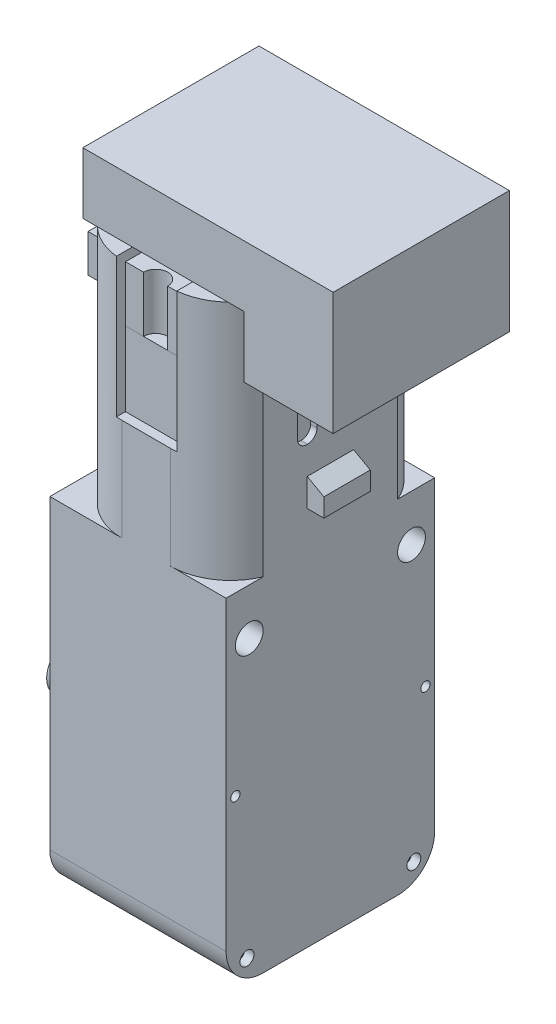
SolidWorks part; units mm, degrees
ref_plane "Alzado" through (0, 0, 0) normal (1, 0, 0) x (0, 1, 0)
ref_plane "Planta" through (0, 0, 0) normal (0, 0, 1) x (0, 1, 0)
ref_plane "Vista lateral" through (0, 0, 0) normal (0, 1, 0) x (-1, 0, 0)
sketch "Croquis1" plane through (0, 0, 0) normal (1, 0, 0) x (0, 1, 0)
  line L1 (-4.84, 11.25) -> (29.66, 11.25)
  line L2 (-7.34, 8.75) -> (-7.34, -8.75)
  line L3 (-4.84, -11.25) -> (29.66, -11.25)
  line L4 (29.66, 11.25) -> (29.66, -11.25)
  line L6 (5.66, 10.25) -> (-4.84, -8.75)
  line L8 (-4.84, 8.75) -> (5.66, -10.25)
  line L9 (-4.84, 0) -> (-0.0045, 0)
  arc A0 (-4.84, -11.25) -> (-7.34, -8.75) centre (-4.84, -8.75) cw
  arc A1 (-4.84, 11.25) -> (-7.34, 8.75) centre (-4.84, 8.75) ccw
  circle A2 centre (5.66, -10.25) radius 0.5
  circle A3 centre (5.66, 10.25) radius 0.5
  circle A4 centre (-0.0045, 0) radius 2.7322
  point P6 (-7.34, -11.25)
  point P9 (-7.34, 11.25)
  point P10 (-7.34, 0)
  dimension "D2" = 2.5
  dimension "D5" = 1
  dimension "D1" = 22.5
  dimension "D3" = 37
  dimension "D8" = 2.5
extrude "Saliente-Extruir2" add sketch "Croquis1" along normal blind 9.5 and the other way blind 9.5 contours L1 A1 L2 A0 L3 L4 A4 A2 A3 | A3 | L9 A4 L6 | L6 A4 L8 | L8 A4 L6 | L6 A4 L8 | L8 A4 L9 | A2 region at (0, 11.5559, 0) region at (0, 5.9069, -9.8315) region at (0, 1.4911, 0) region at (0, -0.0045, 1.745) region at (0, 5.4131, 10.6685) region at (0, -0.0045, -1.745) region at (0, -1.5001, 0.8823) region at (0, -1.5001, -0.8823)
sketch "Croquis2" plane through (0, 0, 0) normal (1, 0, 0) x (0, 1, 0)
  line L0 (-11.84, 3.2804) -> (-10.84, 3.2804)
  line L1 (-7.34, 8.75) -> (-7.34, -8.75) construction
  line L2 (-11.84, -2.5) -> (-11.84, 2.5)
  line L3 (-11.84, 0) -> (-13.0585, 0)
  line L4 (-11.84, -2.5) -> (-7.34, -2.5)
  line L5 (-11.84, -2.5) -> (-11.84, 2.5)
  line L6 (-11.84, 2.5) -> (-7.34, 2.5)
  line L7 (-7.34, -2.5) -> (-7.34, 2.5)
  line L8 (-11.84, -1.34) -> (-11.84, 1.34)
  line L10 (-12.4811, -2.5) -> (-12.4811, -1.5)
  line L11 (-12.4811, 2.5) -> (-12.4811, 1.5)
  circle A0 centre (-9.34, 0) radius 1.5
  dimension "D3" = 1
  dimension "D4" = 4.5
  dimension "D1" = 1
  dimension "D2" = 1
  dimension "D5" = 5
extrude "Saliente-Extruir4" add sketch "Croquis2" along normal blind 1.3 and the other way blind 1.3 contours L4 L7 L6 L5 L2 A0 region at (0, -11.7727, -1.92)
sketch "Croquis3" plane through (-9.5, 0, 0) normal (-1, 0, 0) x (0, -1, 0)
  circle A0 centre (0, 0) radius 2.5
extrude "Cortar-Extruir1" cut sketch "Croquis3" against normal blind 5
sketch "Croquis4" plane through (-9.5, 0, 0) normal (-1, 0, 0) x (0, 0, 1)
  line L0 (-12.6785, 24.66) -> (-12.6785, 5.66)
  line L2 (-11.25, 25.9631) -> (-10.25, 25.9631)
  line L3 (0, -7.34) -> (0, -15.1717)
  line L4 (8.75, -7.34) -> (-8.75, -7.34) construction
  line L5 (11.25, 25.9631) -> (10.25, 25.9631)
  line L6 (10.25, 25.9631) -> (10.25, 5.66)
  line L8 (-10.25, 4.4941) -> (-10.25, 25.9631)
  circle A0 centre (9.75, 5.66) radius 0.5
  circle A1 centre (8.75, -4.84) radius 0.75
  circle A2 centre (-9.75, 5.66) radius 0.5
  circle A3 centre (-8.75, -4.84) radius 0.75
  circle A4 centre (8.75, -4.84) radius 0.75
  circle A5 centre (9.75, 5.66) radius 0.5
  circle A6 centre (-9.75, 5.66) radius 0.5
  circle A7 centre (-8.75, -4.84) radius 0.75
  circle A8 centre (-8.75, -4.84) radius 0.75
  dimension "D3" = 1
  dimension "D4" = 1.5
  dimension "D1" = 19
  dimension "D2" = 1
sketch "Croquis5" plane through (9.5, 0, 0) normal (1, 0, 0) x (0, 1, 0)
  circle A0 centre (-4.84, 8.75) radius 0.75
  circle A1 centre (5.66, 9.75) radius 0.5
  circle A2 centre (5.66, -9.75) radius 0.5
  circle A3 centre (-4.84, -8.75) radius 0.75
extrude "Cortar-Extruir2" cut sketch "Croquis5" against normal blind 1
extrude "Cortar-Extruir3" cut sketch "Croquis4" against normal blind 1 contours A0 | A1 | A3 | A2 region at (-9.5, 5.66, 9.75) region at (-9.5, -4.84, 8.75) region at (-9.5, -4.84, -8.75)
sketch "Croquis6" plane through (-9.5, 0, 0) normal (-1, 0, 0) x (0, 0, 1)
  line L0 (13.1737, 24.66) -> (13.1737, 10.66)
  circle A0 centre (0, 10.66) radius 2
  dimension "D2" = 4
  dimension "D1" = 14
extrude "Saliente-Extruir6" add sketch "Croquis6" along normal blind 2 contours A0 region at (-9.5, 10.66, 0)
sketch "Croquis7" plane through (-9.5, 0, 0) normal (-1, 0, 0) x (0, 0, 1)
  line L0 (-11.25, 26.5829) -> (-10.25, 26.5829)
  line L1 (-12.8476, 24.66) -> (-12.8476, 19.66)
  line L2 (-10.25, 26.5829) -> (-10.25, 19.66)
  line L3 (-10.25, 19.66) -> (-12.8476, 19.66)
  line L4 (0, -11.84) -> (0, -18.0156)
  line L5 (-2.5, -11.84) -> (2.5, -11.84) construction
  line L7 (-7.25, 19.66) -> (-7.25, 21.16)
  line L8 (-7.25, 21.16) -> (-11.25, 21.16)
  circle A0 centre (-8.75, 19.66) radius 1.5
  circle A1 centre (8.75, 19.66) radius 1.5
  dimension "D1" = 1
  dimension "D2" = 5
  dimension "D3" = 1.5
  dimension "D4" = 4
extrude "Cortar-Extruir4" cut sketch "Croquis7" against normal through all contours A0 | A1 region at (-9.5, 19.66, -8.75)
sketch "Croquis8" plane through (0, 29.66, 0) normal (0, 1, 0) x (-1, 0, 0)
  line L1 (-3.5, 11.25) -> (1.7, 11.25)
  line L2 (-9.5, 7.25) -> (-9.5, -7.25)
  line L3 (-3.5, -11.25) -> (1.7, -11.25)
  line L4 (7.7, 7.25) -> (7.7, -7.25)
  line L5 (11.5, 0) -> (15.9145, 0)
  line L7 (11.5, -2) -> (11.5, 2) construction
  line L8 (0, 0) -> (0, 0.7272)
  arc A2 (7.7, 7.25) -> (1.7, 11.25) centre (1.7, 4.75) ccw
  arc A3 (7.7, -7.25) -> (1.7, -11.25) centre (1.7, -4.75) cw
  arc A5 (-3.5, 11.25) -> (-9.5, 7.25) centre (-3.5, 4.75) ccw
  arc A11 (-3.5, -11.25) -> (-9.5, -7.25) centre (-3.5, -4.75) cw
extrude "Saliente-Extruir7" add sketch "Croquis8" along normal blind 26 contours A11 A3 L4 A2 A5 region at (0.9, 29.66, 0)
sketch "Croquis9" plane through (-9.5, 0, 0) normal (-1, 0, 0) x (0, -1, 0)
  line L3 (-8.66, 15.3575) -> (-8.66, -16.1606) construction
  line L4 (-8.66, 15.3575) -> (18.8238, 15.3575)
  line L5 (-8.66, 15.3575) -> (-8.66, -16.1606)
  line L6 (-8.66, -16.1606) -> (18.8238, -16.1606)
  line L7 (18.8238, 15.3575) -> (18.8238, -16.1606)
extrude "Cortar-Extruir5" cut sketch "Croquis9" against normal through all
sketch "Croquis10" plane through (0, 8.66, 0) normal (0, -1, 0) x (-1, 0, 0)
  line L1 (9.5, -11.25) -> (-9.5, -11.25)
  line L2 (9.5, -11.25) -> (9.5, 11.25)
  line L3 (9.5, 11.25) -> (-9.5, 11.25)
  line L4 (-9.5, -11.25) -> (-9.5, 11.25)
sketch "Croquis11" plane through (-9.5, 0, 0) normal (-1, 0, 0) x (0, 0, 1)
  line L1 (13.3634, 18.0947) -> (-15.0337, 18.0947)
  line L2 (13.3634, 18.0947) -> (13.3634, 2.7979)
  line L3 (13.3634, 2.7979) -> (-15.0337, 2.7979)
  line L4 (-15.0337, 18.0947) -> (-15.0337, 2.7979)
extrude "Cortar-Extruir7" cut sketch "Croquis11" against normal through all and the other way through all
sketch "Croquis12" plane through (-9.5, 0, 0) normal (-1, 0, 0) x (0, 0, 1)
  line L0 (-11.25, 29.66) -> (-11.25, 22.66)
  line L1 (-11.25, 18.0947) -> (-11.25, 29.66) construction
  line L3 (-11.25, 22.66) -> (12.1047, 22.66)
  line L4 (-11.25, 22.66) -> (-11.25, 15.491)
  line L5 (-11.25, 15.491) -> (12.1047, 15.491)
  line L6 (12.1047, 22.66) -> (12.1047, 15.491)
  line M2 (-11.25, 29.66) -> (-11.25, 18.0947)
  line M3 (-11.25, 18.0947) -> (11.25, 18.0947)
  line M4 (11.25, 18.0947) -> (11.25, 29.66)
  circle M6 centre (8.75, 19.66) radius 1.5
  circle M7 centre (-8.75, 19.66) radius 1.5
  dimension "D1" = 7
extrude "Cortar-Extruir8" cut sketch "Croquis12" against normal through all contours L3 M2 M3 M4 M6 M7 | L6 L3 L4 L5 M4 M3 region at (-9.5, 20.4918, 0) region at (-9.5, 17.009, 1.1057)
sketch "Croquis14" plane through (0, 22.66, 0) normal (0, -1, 0) x (-1, 0, 0)
  line L1 (9.5, -11.25) -> (-9.5, -11.25)
  line L2 (9.5, -11.25) -> (9.5, 11.25)
  line L3 (9.5, 11.25) -> (-9.5, 11.25)
  line L4 (-9.5, -11.25) -> (-9.5, 11.25)
extrude "Saliente-Extruir9" add sketch "Croquis14" along normal blind 30
sketch "Croquis15" plane through (-9.5, 0, 0) normal (-1, 0, 0) x (0, 0, 1)
  line L0 (0, -7.34) -> (0, -12.8155)
  line L1 (11.25, -7.34) -> (-11.25, -7.34) construction
  line L2 (-11.25, 29.66) -> (-10.25, 29.66)
  line L3 (-7.25, 29.66) -> (-11.25, 29.66) construction
  line L4 (-11.25, 29.66) -> (-11.25, 24.66)
  line L5 (-11.25, -7.34) -> (-11.25, 29.66) construction
  line L6 (-11.25, 24.66) -> (-10.25, 24.66)
  line L7 (-10.25, 24.66) -> (-10.25, 29.66)
  circle A0 centre (-8.75, 24.66) radius 1.5
  circle A1 centre (8.75, 24.66) radius 1.5
  dimension "D3" = 3
  dimension "D1" = 5
  dimension "D2" = 1
extrude "Cortar-Extruir9" cut sketch "Croquis15" against normal through all contours A1 | A0 region at (-9.5, 24.66, -8.75) region at (-9.5, 24.66, 8.75)
sketch "Croquis16" plane through (-9.5, 0, 0) normal (-1, 0, 0) x (0, 0, 1)
  line L0 (11.25, 29.66) -> (11.25, 15.66)
  line L1 (11.25, -7.34) -> (11.25, 29.66) construction
  circle A0 centre (0, 15.66) radius 2
  dimension "D2" = 4
  dimension "D1" = 14
extrude "Saliente-Extruir10" add sketch "Croquis16" along normal blind 2 contours A0 region at (-9.5, 15.66, 0)
sketch "Croquis17" plane through (-9.5, 0, 0) normal (-1, 0, 0) x (0, 0, 1)
  line L0 (11.25, 29.66) -> (11.25, 10.66)
  line L1 (11.25, -7.34) -> (11.25, 29.66) construction
  line L2 (11.25, 10.66) -> (10.75, 10.66)
  line L3 (11.25, -7.34) -> (-11.25, -7.34) construction
  line L4 (14.7504, -3.34) -> (14.7504, -7.34)
  line L5 (9.75, 10.66) -> (9.75, -12.757)
  line L6 (11.25, -3.34) -> (-13.714, -3.34)
  line L7 (11.25, -7.34) -> (7.25, -3.34)
  line L8 (0, -7.34) -> (0, -17.085)
  line L9 (-11.25, -3.34) -> (-11.25, -7.34)
  line L10 (-11.25, -7.34) -> (-7.25, -7.34)
  line L11 (-7.25, -7.34) -> (7.25, -7.34)
  line L12 (7.25, -7.34) -> (11.25, -7.34)
  line L13 (11.25, -3.34) -> (11.25, -7.34)
  line L14 (11.25, -7.34) -> (7.25, -7.34)
  line L15 (11.25, -3.34) -> (11.25, -7.34)
  circle A0 centre (10.25, 10.66) radius 0.5
  arc A1 (7.25, -7.34) -> (9.75, -0.2175) centre (7.25, -3.34) ccw
  circle A4 centre (9, -5.09) radius 0.75
  circle A5 centre (-9, -5.09) radius 0.75
  arc A6 (-7.25, -7.34) -> (-11.25, -3.34) centre (-7.25, -3.34) cw
  circle A7 centre (-10.25, 10.66) radius 0.5
  arc A8 (7.25, -7.34) -> (11.25, -3.34) centre (7.25, -3.34) ccw
  dimension "D3" = 1
  dimension "D4" = 8
  dimension "D5" = 1.5
  dimension "D1" = 19
  dimension "D2" = 0.5
sketch "Croquis18" plane through (-9.5, 0, 0) normal (-1, 0, 0) x (0, 0, 1)
extrude "Cortar-Extruir10" cut sketch "Croquis17" against normal through all contours A0 | A4 L7 | L7 A4 | A7 | A5 region at (-9.5, 10.66, 10.25) region at (-9.5, -4.8649, 9.2251) region at (-9.5, -5.3151, 8.7749) region at (-9.5, 10.66, -10.25)
sketch "Croquis19" plane through (-9.5, 0, 0) normal (-1, 0, 0) x (0, 0, 1)
  line L0 (11.25, -7.34) -> (11.25, -3.34)
  line L1 (11.25, -7.34) -> (11.25, 29.66) construction
  line L2 (0, -7.34) -> (0, -13.8514)
  line L3 (11.25, -7.34) -> (7.25, -7.34)
  line L4 (11.25, -7.34) -> (-11.25, -7.34) construction
  line L5 (-11.25, -7.34) -> (-7.25, -7.34)
  line L6 (-11.25, -7.34) -> (-11.25, -3.34)
  arc A0 (7.25, -7.34) -> (11.25, -3.34) centre (7.25, -3.34) ccw
  arc A1 (-7.25, -7.34) -> (-11.25, -3.34) centre (-7.25, -3.34) cw
  line M9 (-11.25, 29.66) -> (-11.25, -7.34)
  line M10 (-11.25, -7.34) -> (11.25, -7.34)
  line M11 (11.25, -7.34) -> (11.25, 29.66)
  dimension "D1" = 8
sketch "Croquis20" plane through (0, -7.34, 0) normal (0, -1, 0) x (1, 0, 0)
  line L5 (-8.6868, 10.6536) -> (8.5298, 10.6536)
  line L6 (-8.6868, 10.6536) -> (-8.6868, -10.8334)
  line L7 (-8.6868, -10.8334) -> (8.5298, -10.8334)
  line L8 (8.5298, 10.6536) -> (8.5298, -10.8334)
  line L9 (2.0429, 4.3316) -> (2.816, 4.3316)
  line L10 (2.0429, 4.3316) -> (2.0429, 4.8022)
  line L11 (2.0429, 4.8022) -> (2.816, 4.8022)
  line L12 (2.816, 4.3316) -> (2.816, 4.8022)
extrude "Saliente-Extruir12" add sketch "Croquis20" against normal blind 24 contours L10 L9 L12 L11
sketch "Croquis21" plane through (0, -7.34, 0) normal (0, -1, 0) x (-1, 0, 0)
  line L0 (9.5, -11.25) -> (-9.5, -11.25) construction
  line L1 (8.3272, -11.25) -> (-8.5298, -11.25)
  line L2 (8.3272, -11.25) -> (8.3272, 11.25)
  line L3 (8.3272, 11.25) -> (-8.5298, 11.25)
  line L4 (-8.5298, -11.25) -> (-8.5298, 11.25)
  line L5 (9.5, 11.25) -> (-9.5, 11.25) construction
extrude "Saliente-Extruir13" add sketch "Croquis21" against normal blind 24
extrude "Cortar-Extruir11" cut sketch "Croquis19" against normal through all contours A0 M10 M11 | A1 M10 M9 region at (-9.5, -6.4465, 10.3565) region at (-9.5, -6.4465, -10.3565)
sketch "Croquis22" plane through (-9.5, 0, 0) normal (-1, 0, 0) x (0, 0, 1)
  line L0 (7.25, -7.34) -> (17.3359, -7.34)
  line L1 (11.25, -7.34) -> (11.25, 3.86)
  line L2 (11.25, -3.34) -> (11.25, 29.66) construction
  line L3 (11.25, 3.86) -> (-11.25, 3.86)
  line L4 (-11.25, -3.34) -> (-11.25, 29.66) construction
  circle A0 centre (0, 3.86) radius 2.6
  dimension "D2" = 5.2
  dimension "D1" = 11.2
extrude "Cortar-Extruir12" cut sketch "Croquis22" against normal blind 5 contours L3 A0 | L3 A0 region at (-9.5, 2.7565, 0) region at (-9.5, 4.9635, 0)
sketch "Croquis23" plane through (-9.5, 0, 0) normal (-1, 0, 0) x (0, 0, 1)
  circle A0 centre (0, 3.86) radius 2.6
  circle A1 centre (0, 3.86) radius 2.75
  dimension "D1" = 5.5
extrude "Saliente-Extruir14" add sketch "Croquis23" along normal blind 0.5 draft 8 contours A1 | A0
sketch "Croquis24" plane through (0, -7.34, 0) normal (0, -1, 0) x (1, 0, 0)
  line L1 (-1.25, -2.5) -> (1.25, -2.5)
  line L2 (-1.25, -2.5) -> (-1.25, 2.5)
  line L3 (-1.25, 2.5) -> (1.25, 2.5)
  line L4 (1.25, -2.5) -> (1.25, 2.5)
  line L5 (-1.25, -2.5) -> (1.25, 2.5) construction
  line L6 (-1.25, 2.5) -> (1.25, -2.5) construction
  point P0 (0, 0)
  dimension "D1" = 2.5
  dimension "D2" = 5
extrude "Saliente-Extruir15" add sketch "Croquis24" along normal blind 4.7
sketch "Croquis25" plane through (-1.25, 0, 0) normal (-1, 0, 0) x (0, 0, 1)
  line L0 (2.5, -12.04) -> (-2.5, -12.04) construction
  circle A0 centre (0, -9.64) radius 1.4
  dimension "D1" = 2.8
  dimension "D2" = 2.4
extrude "Cortar-Extruir13" cut sketch "Croquis25" against normal blind 4.7
sketch "Croquis26" plane through (-7.7, 0, 0) normal (-1, 0, 0) x (0, -1, 0)
  line L0 (-29.66, -7.25) -> (-33.66, -7.25)
  line L1 (-55.66, -7.25) -> (-29.66, -7.25) construction
  line L2 (-33.66, -7.25) -> (-33.66, 7.25)
  line L3 (-55.66, 7.25) -> (-29.66, 7.25) construction
  line L5 (-36.66, 2.5) -> (-33.66, 2.5)
  line L6 (-36.66, 2.5) -> (-36.66, -2.5)
  line L7 (-36.66, -2.5) -> (-33.66, -2.5)
  line L8 (-33.66, 2.5) -> (-33.66, -2.5)
  line L9 (-36.66, 2.5) -> (-33.66, -2.5) construction
  line L10 (-36.66, -2.5) -> (-33.66, 2.5) construction
  point P5 (-35.16, 0)
  point P14 (-33.66, 0)
  dimension "D1" = 4
  dimension "D2" = 3
  dimension "D3" = 5
extrude "Saliente-Extruir17" add sketch "Croquis26" along normal blind 2 and the other way blind 19 contours L6 L7 L2 L5 region at (-7.7, 35.16, 0)
sketch "Croquis27" plane through (0, 0, 0) normal (0, 0, 1) x (0, 1, 0)
  line L0 (33.66, 9.7) -> (35.66, 9.7)
  line L1 (36.66, 9.7) -> (33.66, 9.7) construction
  line L2 (35.66, 9.7) -> (35.66, -11.3)
  line L3 (36.66, -11.3) -> (33.66, -11.3) construction
  line L4 (35.66, 9.7) -> (36.66, 7.7)
  line L5 (36.66, 7.7) -> (36.66, 9.7)
  line L6 (36.66, 9.7) -> (35.66, 9.7)
  line L7 (35.66, -11.3) -> (36.66, -9.5)
  line L8 (36.66, -9.5) -> (36.66, -11.3)
  line L9 (36.66, -11.3) -> (35.66, -11.3)
  dimension "D1" = 2
extrude "Cortar-Extruir14" cut sketch "Croquis27" against normal through all and the other way through all contours L5 L6 L4 | L9 L8 L7 region at (10.7, 36.3267, 0) region at (-9.0333, 36.3267, 0)
sketch "Croquis28" plane through (-7.7, 0, 0) normal (-1, 0, 0) x (0, -1, 0)
  line L0 (-36.66, -2.5) -> (-39.66, -2.5)
  line L1 (-36.66, 0) -> (-38.0942, 0)
  line L2 (-45.66, -1.4465) -> (-40.66, -1.4465)
  line L3 (-46.66, -2.4465) -> (-46.66, -2.5535)
  line L4 (-45.66, -3.5535) -> (-40.66, -3.5535)
  line L5 (-39.66, -2.4465) -> (-39.66, -2.5535)
  line L6 (-46.66, -1.4465) -> (-39.66, -3.5535) construction
  line L7 (-46.66, -3.5535) -> (-39.66, -1.4465) construction
  line L8 (-36.66, 2.5) -> (-36.66, -2.5) construction
  line L9 (-45.66, 3.5535) -> (-40.66, 3.5535)
  line L10 (-39.66, 2.4465) -> (-39.66, 2.5535)
  line L11 (-45.66, 1.4465) -> (-40.66, 1.4465)
  line L12 (-46.66, 2.4465) -> (-46.66, 2.5535)
  arc A0 (-45.66, -3.5535) -> (-46.66, -2.5535) centre (-45.66, -2.5535) cw
  arc A1 (-46.66, -2.4465) -> (-45.66, -1.4465) centre (-45.66, -2.4465) cw
  arc A2 (-39.66, -2.5535) -> (-40.66, -3.5535) centre (-40.66, -2.5535) cw
  arc A3 (-39.66, -2.4465) -> (-40.66, -1.4465) centre (-40.66, -2.4465) ccw
  arc A4 (-39.66, 2.5535) -> (-40.66, 3.5535) centre (-40.66, 2.5535) ccw
  arc A5 (-39.66, 2.4465) -> (-40.66, 1.4465) centre (-40.66, 2.4465) cw
  arc A6 (-45.66, 3.5535) -> (-46.66, 2.5535) centre (-45.66, 2.5535) ccw
  arc A7 (-46.66, 2.4465) -> (-45.66, 1.4465) centre (-45.66, 2.4465) ccw
  point P2 (-43.16, -2.5)
  dimension "D3" = 1
  dimension "D1" = 3
  dimension "D2" = 7
extrude "Cortar-Extruir15" cut sketch "Croquis28" against normal through all contours L12 A7 L11 A5 L10 A4 L9 A6 | L2 A3 L5 A2 L4 A0 L3 A1 region at (-7.7, 43.16, 2.5)
sketch "Croquis29" plane through (9.5, 0, 0) normal (1, 0, 0) x (0, 1, 0)
  line L0 (40.66, -1.4465) -> (45.66, -1.4465) construction
  line L5 (36.66, 0) -> (38.1303, 0)
  line L6 (36.66, -2.5) -> (36.66, 2.5) construction
  line L7 (40.66, -3.5535) -> (45.66, -3.5535) construction
  line L8 (40.66, -1.4465) -> (50.66, -1.4465)
  line L13 (40.66, -1.4465) -> (40.66, -3.5535)
  line L14 (40.66, -3.5535) -> (50.66, -3.5535)
  line L15 (51.66, -2.4465) -> (51.66, -2.5535)
  line L16 (40.66, 3.5535) -> (50.66, 3.5535)
  line L17 (51.66, 2.4465) -> (51.66, 2.5535)
  line L18 (40.66, 1.4465) -> (50.66, 1.4465)
  line L19 (40.66, 1.4465) -> (40.66, 3.5535)
  arc A1 (51.8241, -1.5254) -> (51.8281, -1.6145) centre (52.8241, -1.5254) ccw
  arc A2 (51.66, -2.5535) -> (50.66, -3.5535) centre (50.66, -2.5535) cw
  arc A3 (51.66, -2.4465) -> (50.66, -1.4465) centre (50.66, -2.4465) ccw
  arc A4 (51.66, 2.5535) -> (50.66, 3.5535) centre (50.66, 2.5535) ccw
  arc A5 (51.66, 2.4465) -> (50.66, 1.4465) centre (50.66, 2.4465) cw
  point P16 (52.66, -3.4465)
  point P19 (51.66, -3.5535)
  point P24 (39.66, -1.4465)
  arc M37 (45.66, -1.4465) -> (46.66, -2.4465) centre (45.66, -2.4465) cw
  line M38 (46.66, -2.4465) -> (46.66, -2.5535)
  arc M39 (46.66, -2.5535) -> (45.66, -3.5535) centre (45.66, -2.5535) cw
  arc M44 (45.66, 3.5535) -> (46.66, 2.5535) centre (45.66, 2.5535) cw
  line M45 (46.66, 2.5535) -> (46.66, 2.4465)
  arc M46 (46.66, 2.4465) -> (45.66, 1.4465) centre (45.66, 2.4465) cw
  dimension "D2" = 1
  dimension "D1" = 11
extrude "Cortar-Extruir16" cut sketch "Croquis29" against normal blind 7 contours A5 L17 A4 L16 L18 M44 M45 M46 | L15 A3 L8 L14 A2 M37 M38 M39 region at (9.5, 48.9563, -2.5) region at (9.5, 48.9563, 2.5)
sketch "Croquis30" plane through (0, 0, 0) normal (0, 0, 1) x (0, 1, 0)
  line L0 (55.66, 8.7) -> (48.16, 8.7)
  line L1 (55.66, 8.7) -> (55.66, 7.7)
  line L2 (55.66, 7.7) -> (55.66, 6.2)
  line L3 (55.66, 1.7) -> (55.66, 7.7) construction
  line L4 (55.66, 8.7) -> (55.66, 9.8676)
  line L5 (48.16, 8.7) -> (55.66, 8.7)
  line L6 (48.16, 8.7) -> (48.16, 7.7)
  line L7 (48.16, 7.7) -> (55.66, 7.7)
  line L8 (55.66, 8.7) -> (55.66, 7.7)
  line L9 (55.66, 9.8676) -> (54.66, 9.8676)
  line L10 (48.16, 8.7) -> (48.16, 10.3949)
  line L11 (48.16, 10.3949) -> (49.16, 10.3949)
  line L12 (49.16, 10.3949) -> (49.16, 7.7)
  line L13 (54.66, 9.8676) -> (54.66, 7.7)
  dimension "D1" = 7.5
  dimension "D2" = 1.5
  dimension "D3" = 1
  dimension "D4" = 1
  dimension "D5" = 1
extrude "Saliente-Extruir18" add sketch "Croquis30" along normal blind 3.75 and the other way blind 3.75 contours L6 L5 L8 L7
sketch "Croquis31" plane through (0, 0, 0) normal (0, 0, 1) x (0, 1, 0)
  line L0 (55.66, 8.7) -> (55.66, 9.5141)
  line L1 (55.66, 9.5141) -> (54.66, 9.5141)
  line L2 (48.16, 8.9893) -> (49.16, 8.9893)
  line L3 (49.16, 8.9893) -> (49.16, 7.7)
  line L4 (55.66, 7.7) -> (29.66, 7.7) construction
  line L5 (49.16, 7.7) -> (54.66, 7.7)
  line L7 (49.16, 7.7) -> (54.66, 7.7)
  line L8 (49.16, 7.7) -> (49.16, 6.2)
  line L9 (49.16, 6.2) -> (54.66, 6.2)
  line L10 (54.66, 7.7) -> (54.66, 6.2)
  dimension "D1" = 1
  dimension "D2" = 1
  dimension "D3" = 1.5
extrude "Cortar-Extruir17" cut sketch "Croquis31" against normal through all and the other way through all contours L10 L5 L8 L9 region at (-6.95, 51.91, 0)
sketch "Croquis32" plane through (0, 0, 0) normal (0, 0, 1) x (0, 1, 0)
  line L0 (48.16, 7.7) -> (48.16, 8.7)
  line L1 (48.16, 8.7) -> (48.926, 8.7)
  line L2 (48.16, 8.7) -> (55.66, 8.7) construction
  line L3 (48.926, 8.7) -> (48.16, 7.7)
extrude "Cortar-Extruir18" cut sketch "Croquis32" against normal through all and the other way through all
sketch "Croquis33" plane through (0, 0, 3.75) normal (0, 0, 1) x (1, 0, 0)
  line L0 (-7.7, 55.66) -> (-8.7, 55.3867)
  line L1 (-8.7, 48.926) -> (-8.7, 55.66) construction
  line L2 (-8.7, 55.3867) -> (-7.7, 55.3867)
  line L3 (-7.7, 55.66) -> (-7.7, 54.66) construction
  line L4 (-7.7, 55.3867) -> (-7.7, 55.66)
  line L5 (-8.7, 55.3867) -> (-8.7, 55.66)
  line L6 (-8.7, 55.66) -> (-7.7, 55.66)
  line L7 (-8.7, 55.3867) -> (-8.7, 55.66)
  line M4 (-8.7, 55.66) -> (-8.7, 48.926)
  line M9 (-7.7, 55.66) -> (-8.7, 55.66)
extrude "Cortar-Extruir22" cut sketch "Croquis33" against normal through all and the other way through all contours L0 M9 M4 region at (-8.3667, 55.5689, 3.75)
sketch "Croquis34" plane through (0, 55.66, 0) normal (0, 1, 0) x (1, 0, 0)
  line L5 (3.5, -11.25) -> (-1.7, -11.25)
  line L6 (0.9, -11.25) -> (0.9, -13.2757)
  line L7 (12.6416, 0) -> (17.759, 0)
  line L8 (4.15, -8.25) -> (-2.35, -8.25)
  line L9 (4.15, -8.25) -> (4.15, -11.25)
  line L10 (4.15, -11.25) -> (-2.35, -11.25)
  line L11 (-2.35, -8.25) -> (-2.35, -11.25)
  line L12 (4.15, -8.25) -> (-2.35, -11.25) construction
  line L13 (4.15, -11.25) -> (-2.35, -8.25) construction
  line L14 (4.15, 11.25) -> (-2.35, 11.25)
  line L15 (-2.35, 8.25) -> (-2.35, 11.25)
  line L16 (4.15, 8.25) -> (-2.35, 8.25)
  line L17 (4.15, 8.25) -> (4.15, 11.25)
  point P4 (0.9, -9.75)
  arc M9 (-7.7, -7.25) -> (-1.7, -11.25) centre (-1.7, -4.75) ccw
  line M10 (-1.7, -11.25) -> (3.5, -11.25)
  arc M11 (3.5, -11.25) -> (9.5, -7.25) centre (3.5, -4.75) ccw
  arc M13 (9.5, 7.25) -> (3.5, 11.25) centre (3.5, 4.75) ccw
  line M14 (3.5, 11.25) -> (-1.7, 11.25)
  arc M15 (-1.7, 11.25) -> (-7.7, 7.25) centre (-1.7, 4.75) ccw
  dimension "D1" = 6.5
  dimension "D2" = 3
extrude "Cortar-Extruir23" cut sketch "Croquis34" against normal blind 15 contours L8 L11 L5 L9 M9 M10 M11 | L16 L17 L15 M13 M14 M15 region at (0.9, 55.66, 9.7489) region at (0.9, 55.66, -9.7489)
sketch "Croquis35" plane through (0, 55.66, 0) normal (0, 1, 0) x (-1, 0, 0)
  line L0 (-9.5, 0) -> (3.1, 0)
  line L1 (-9.5, 11.25) -> (-9.5, -11.25) construction
  line L2 (7.7, -3.75) -> (7.7, 3.75) construction
  line L3 (-9.5, 7.25) -> (7.7, 7.25)
  line L4 (-5.9, 0) -> (3.1, 0)
  line L5 (3.1, 0) -> (3.1, 3)
  line L6 (3.1, 3) -> (3.1, -3)
  line L7 (4.1, 0) -> (7.7, 0)
  arc A0 (3.1, 3) -> (3.1, -3) centre (-0.9, 0) ccw
  dimension "D1" = 10
  dimension "D2" = 9
extrude "Cortar-Extruir24" cut sketch "Croquis35" against normal blind 5 contours L5 A0 L0 | L0 A0 L6 region at (1.1418, 55.66, 2.1759) region at (1.1418, 55.66, -2.1759)
sketch "Croquis37" plane through (0, 39.66, 0) normal (0, 1, 0) x (1, 0, 0)
  line L5 (8.8118, -6.8201) -> (-6.9662, -6.8201)
  line L6 (8.8118, -6.8201) -> (8.8118, 7.9883)
  line L7 (8.8118, 7.9883) -> (-6.9662, 7.9883)
  line L8 (-6.9662, -6.8201) -> (-6.9662, 7.9883)
extrude "Saliente-Extruir19" add sketch "Croquis37" along normal blind 11 separate body
sketch "Croquis38" plane through (-6.2, 0, 0) normal (-1, 0, 0) x (0, 0, 1)
  line L0 (-9.4404, 54.66) -> (-9.4404, 49.16) construction
  line L1 (9.4404, 54.66) -> (-9.4404, 54.66)
  line L2 (9.4404, 54.66) -> (9.4404, 50.5786)
  line L3 (9.4404, 50.5786) -> (-9.4404, 50.5786)
  line L4 (-9.4404, 54.66) -> (-9.4404, 50.5786)
extrude "Saliente-Extruir21" add sketch "Croquis38" along normal blind 1 separate body
sketch "Croquis39" plane through (-7.2, 0, 0) normal (-1, 0, 0) x (0, 0, 1)
  line L0 (3.75, 54.66) -> (7.25, 54.66) construction
  line L1 (4.5442, 54.66) -> (-4.5793, 54.66)
  line L2 (4.5442, 54.66) -> (4.5442, 50.5786)
  line L3 (4.5442, 50.5786) -> (-4.5793, 50.5786)
  line L4 (-4.5793, 54.66) -> (-4.5793, 50.5786)
  line L5 (-9.4404, 50.5786) -> (9.4404, 50.5786) construction
extrude "Saliente-Extruir23" add sketch "Croquis39" along normal blind 0.6 separate body
sketch "Croquis40" plane through (0, 40.66, 0) normal (0, 1, 0) x (-1, 0, 0)
  line L0 (2.35, -8.25) -> (2.35, -11.2174) construction
  line L1 (-4.15, -8.25) -> (2.35, -8.25)
  line L2 (-4.15, -8.25) -> (-4.15, -10.25)
  line L3 (-4.15, -10.25) -> (2.35, -10.25)
  line L4 (2.35, -8.25) -> (2.35, -10.25)
  line L5 (-11.3, 0) -> (-17.9203, 0)
  line L6 (-11.3, 2.5) -> (-11.3, -2.5) construction
  line L7 (-4.15, 10.25) -> (2.35, 10.25)
  line L8 (2.35, 8.25) -> (2.35, 10.25)
  line L9 (-4.15, 8.25) -> (2.35, 8.25)
  line L10 (-4.15, 8.25) -> (-4.15, 10.25)
  line M10 (2.35, -8.25) -> (-4.15, -8.25)
  line M11 (-4.15, -8.25) -> (-4.15, -11.2174)
  line M15 (2.35, -11.2174) -> (2.35, -8.25)
  dimension "D1" = 2
extrude "Saliente-Extruir24" add sketch "Croquis40" along normal blind 8 separate body contours L10 L9 L8 L7 | L3 M11 M15 M10 region at (0.9, 40.66, -9.25) region at (0.9, 40.66, 9.25)
sketch "Croquis41" plane through (0, 50.66, 0) normal (0, 1, 0) x (1, 0, 0)
  circle A0 centre (0.9, 0) radius 1
  dimension "D1" = 2
extrude "Saliente-Extruir26" add sketch "Croquis41" along normal blind 7 separate body contours A0
sketch "Croquis42" plane through (0, 48.66, 0) normal (0, 1, 0) x (1, 0, 0)
  line L0 (4.15, -10.25) -> (-2.35, -10.25) construction
  line L1 (-2.35, -8.25) -> (4.15, -8.25)
  line L2 (-2.35, -8.25) -> (-2.35, -10.25)
  line L3 (-2.35, -10.25) -> (-0.4059, -10.25)
  line L4 (4.15, -8.25) -> (4.15, -10.25)
  line L5 (2.2059, -10.25) -> (4.15, -10.25)
  line L6 (-11.5, 0) -> (-14.0238, 0)
  line L7 (-11.5, 2) -> (-11.5, -2) construction
  line L8 (2.2059, 10.25) -> (4.15, 10.25)
  line L9 (4.15, 8.25) -> (4.15, 10.25)
  line L10 (-2.35, 8.25) -> (4.15, 8.25)
  line L11 (-2.35, 8.25) -> (-2.35, 10.25)
  line L12 (-2.35, 10.25) -> (-0.4059, 10.25)
  arc A0 (2.2059, -10.25) -> (-0.4059, -10.25) centre (0.9, -10.25) ccw
  arc A1 (2.2059, 10.25) -> (-0.4059, 10.25) centre (0.9, 10.25) cw
  line M8 (4.15, -10.25) -> (4.15, -8.25)
  line M9 (4.15, -8.25) -> (-2.35, -8.25)
  line M10 (-2.35, -8.25) -> (-2.35, -10.25)
  line M11 (-2.35, -10.25) -> (4.15, -10.25)
extrude "Saliente-Extruir27" add sketch "Croquis42" along normal blind 6 separate body contours A0 M11 M8 M9 M10 | L8 A1 L12 L11 L10 L9 region at (0.9, 48.66, 8.318) region at (3.1779, 48.66, -10.182)
sketch "Croquis43" plane through (0, 50.66, 0) normal (0, 1, 0) x (1, 0, 0)
  line L0 (-3.1, -3) -> (-3.1, 3)
  arc A0 (-3.1, -3) -> (-3.1, 3) centre (0.9, 0) ccw
extrude "Saliente-Extruir28" add sketch "Croquis43" along normal blind 6 separate body contours A0 L0
sketch "Croquis44" plane through (0, 50.66, 0) normal (0, 1, 0) x (1, 0, 0)
  line L1 (9.1152, -4.8548) -> (3.9007, -4.8548)
  line L2 (9.1152, -4.8548) -> (9.1152, 4.72)
  line L3 (9.1152, 4.72) -> (3.9007, 4.72)
  line L4 (3.9007, -4.8548) -> (3.9007, 4.72)
extrude "Saliente-Extruir29" add sketch "Croquis44" along normal blind 2 separate body
sketch "Croquis46" plane through (-7.2, 0, 0) normal (-1, 0, 0) x (0, 0, 1)
  line L0 (4.5442, 50.5786) -> (4.5442, 54.66) construction
  line L4 (8.1975, 52.779) -> (8.1975, 52.4596)
  line L5 (0, 57.66) -> (0, 63.4537)
  line L6 (1, 57.66) -> (-1, 57.66) construction
  line L7 (-8.1975, 52.779) -> (-8.1975, 52.4596)
  line L12 (-4.5442, 53.779) -> (-7.1975, 53.779)
  line L13 (-4.5442, 51.4596) -> (-4.5442, 53.779)
  line L14 (4.5442, 51.4596) -> (7.1975, 51.4596)
  line L15 (4.5442, 51.4596) -> (4.5442, 53.779)
  line L16 (4.5442, 53.779) -> (7.1975, 53.779)
  line L17 (8.1975, 51.4596) -> (8.1975, 53.779)
  line L18 (-4.5442, 51.4596) -> (-7.1975, 51.4596)
  arc A0 (7.1975, 51.4596) -> (8.1975, 52.4596) centre (7.1975, 52.4596) ccw
  arc A1 (7.1975, 53.779) -> (8.1975, 52.779) centre (7.1975, 52.779) cw
  circle A2 centre (7.1975, 52.6193) radius 0.6976
  circle A3 centre (-7.1975, 52.6193) radius 0.6976
  arc A4 (-7.1975, 51.4596) -> (-8.1975, 52.4596) centre (-7.1975, 52.4596) cw
  arc A5 (-7.1975, 53.779) -> (-8.1975, 52.779) centre (-7.1975, 52.779) ccw
  point P0 (4.5442, 52.6193)
  point P9 (4.5442, 53.779)
  dimension "D1" = 1
extrude "Saliente-Extruir32" add sketch "Croquis46" along normal blind 0.4 separate body contours A1 L16 L15 L14 A0 L4 A2 | L12 A5 L7 A4 L18 L13 A3 region at (-7.2, 52.6193, 6.0712) region at (-7.2, 52.6193, -6.0712)
sketch "Croquis47" plane through (-4.5, 0, 0) normal (-1, 0, 0) x (0, 0, 1)
  circle A0 centre (0, 3.86) radius 2.6
  dimension "D1" = 5.2
extrude "Saliente-Extruir33" add sketch "Croquis47" along normal blind 14 separate body
sketch "Croquis48" plane through (-18.5, 0, 0) normal (-1, 0, 0) x (0, 0, 1)
  line L0 (0, 5.61) -> (2.9802, 5.61)
  line L1 (2.9802, 5.61) -> (-2.9064, 5.61)
  line L2 (-2.9064, 5.61) -> (0, 2.11)
  line L3 (0, 2.11) -> (3.1399, 2.11)
  line L4 (3.1399, 2.11) -> (-3.086, 2.11)
  circle A0 centre (0, 3.86) radius 2.6
  circle A1 centre (0, 3.86) radius 1.75
  circle M3 centre (0, 3.86) radius 2.6
  dimension "D1" = 3.5
extrude "Cortar-Extruir25" cut sketch "Croquis48" against normal blind 8 contours L1 L0 M3 | L3 L4 M3 region at (-18.5, 5.9553, 0) region at (-18.5, 1.7647, 0)
sketch "Croquis49" plane through (-18.5, 0, 0) normal (-1, 0, 0) x (0, 0, 1)
  circle A0 centre (0, 3.86) radius 1
extrude "Cortar-Extruir26" cut sketch "Croquis49" against normal blind 8
sketch "草圖1" plane through (0, 55.66, 0) normal (0, 1, 0) x (1, 0, 0)
  line L0 (0.9, 0) -> (-17.59, 0) construction
  line L1 (-7.7, -9.5) -> (19.3, -9.5)
  line L2 (-7.7, -9.5) -> (-7.7, 9.5)
  line L3 (-7.7, 9.5) -> (19.3, 9.5)
  line L4 (19.3, -9.5) -> (19.3, 9.5)
  dimension "D1" = 27
  dimension "D2" = 9.5
  dimension "D3" = 9.5
extrude "填料-伸長1" add sketch "草圖1" along normal blind 6.6
sketch "草圖2" plane through (0, 55.66, 0) normal (0, -1, 0) x (1, 0, 0)
  line L0 (7.9371, 9.5) -> (19.3, 9.5)
  line L1 (19.3, 9.5) -> (19.3, -9.5)
  line L2 (19.3, -9.5) -> (7.9371, -9.5)
  line L3 (19.3, -9.5) -> (7.9371, -9.5) construction
  line L5 (19.3, -9.5) -> (9.6816, -9.5)
  line L6 (19.3, -9.5) -> (19.3, 9.5)
  line L7 (19.3, 9.5) -> (9.6816, 9.5)
  line L8 (9.6816, -9.5) -> (9.6816, 9.5)
extrude "填料-伸長5" add sketch "草圖2" along normal blind 6.6 contours L6 L5 L8 L7
